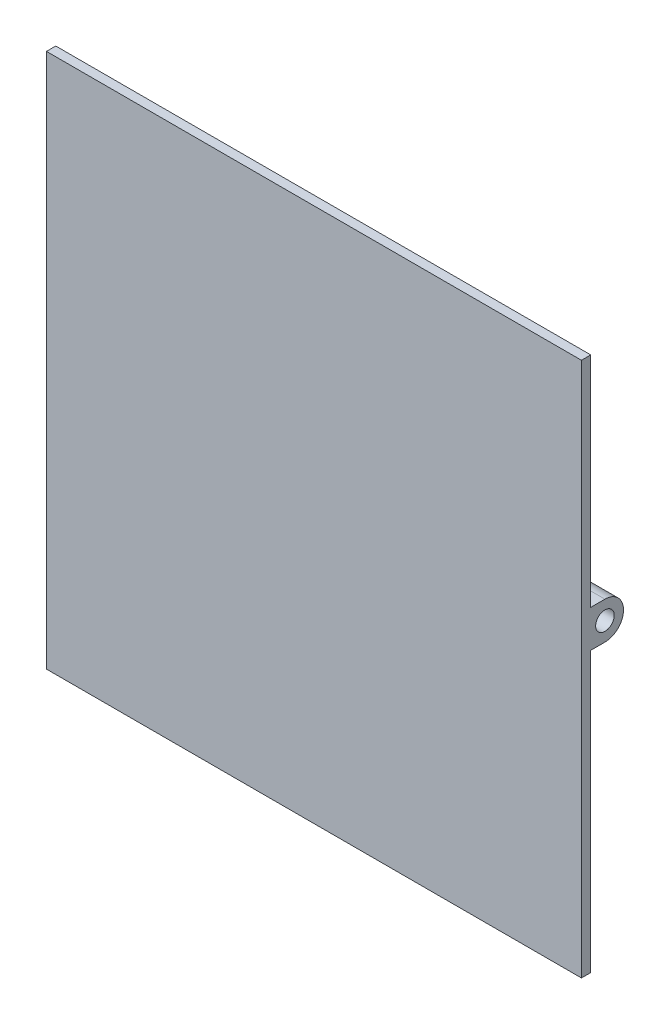
SolidWorks part; units mm, degrees
ref_plane "Płaszczyzna przednia" through (0, 0, 0) normal (0, 0, 1) x (1, 0, 0)
ref_plane "Płaszczyzna górna" through (0, 0, 0) normal (0, 1, 0) x (1, 0, 0)
ref_plane "Płaszczyzna prawa" through (0, 0, 0) normal (1, 0, 0) x (0, 0, -1)
sketch "Szkic1" plane through (0, 0, 0) normal (0, 0, 1) x (1, 0, 0)
  line L0 (0, -57.5) -> (115, -57.5) construction
  line L1 (0, 0) -> (115, 0)
  line L2 (0, 0) -> (0, -115)
  line L3 (0, -115) -> (115, -115)
  line L4 (115, 0) -> (115, -115)
  dimension "D1" = 115
  dimension "D2" = 115
extrude "Dodanie-wyciągnięcie1" add sketch "Szkic1" along normal blind 2
sketch "Szkic3" plane through (115, 0, 0) normal (1, 0, 0) x (0, 0, -1)
  line L0 (0, -115) -> (0, 0) construction
  line L1 (0, -47) -> (3.0506, -47)
  line L2 (0, -47) -> (0, -55)
  line L3 (0, -55) -> (3.0506, -55)
  line L6 (-2, -115) -> (0, -115) construction
  arc A0 (3.0506, -55) -> (3.0506, -47) centre (3.0506, -51) ccw
  dimension "D1" = 8
  dimension "D2" = 60
extrude "Dodanie-wyciągnięcie2" add sketch "Szkic3" against normal up to surface (115 mm away) up to face at (0, -57.5, 1)
sketch "Szkic5" plane through (115, 0, 0) normal (1, 0, 0) x (0, 0, -1)
  circle A0 centre (3.0506, -51) radius 2
  arc A1 (3.0506, -55) -> (3.0506, -47) centre (3.0506, -51) ccw construction
  dimension "D1" = 4
extrude "Wytnij-wyciągnięcie1" cut sketch "Szkic5" against normal through all
